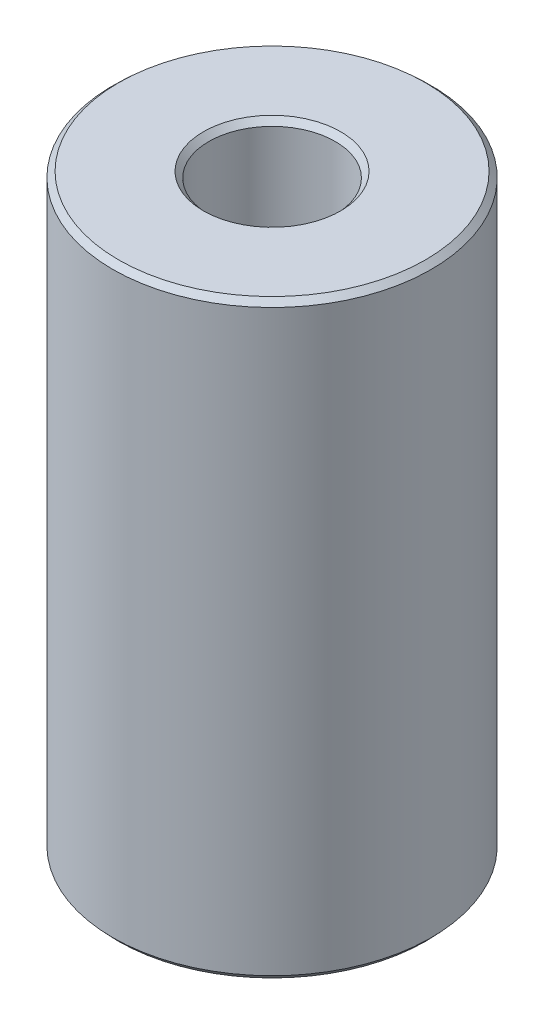
SolidWorks part; units mm, degrees
ref_plane "Front Plane" through (0, 0, 0) normal (0, 0, 1) x (1, 0, 0)
ref_plane "Top Plane" through (0, 0, 0) normal (0, 1, 0) x (1, 0, 0)
ref_plane "Right Plane" through (0, 0, 0) normal (1, 0, 0) x (0, 0, -1)
sketch "Sketch1" plane through (0, 0, 0) normal (0, 1, 0) x (1, 0, 0)
  circle A0 centre (0, 0) radius 15
  dimension "SLEEVE_OD" = 30
extrude "Boss-Extrude1" add sketch "Sketch1" along normal blind 55.5728
sketch "Sketch2" plane through (0, 0, 0) normal (0, 1, 0) x (1, 0, 0)
  circle A0 centre (0, 0) radius 5.9562
  dimension "BORE_D" = 11.9125
extrude "Cut-Extrude1" cut sketch "Sketch2" along normal through all
chamfer "Chamfer1" distance 0.5092 angle 46.851 4 edges at (0, 55.5728, 5.9562) (0, 0, 5.9562) (0, 0, 15) (0, 55.5728, 15) first distance on face at (0, 55.5728, 5.9562) first distance on face at (0, 0, 5.9562) first distance on face at (0, 55.5728, 15)
